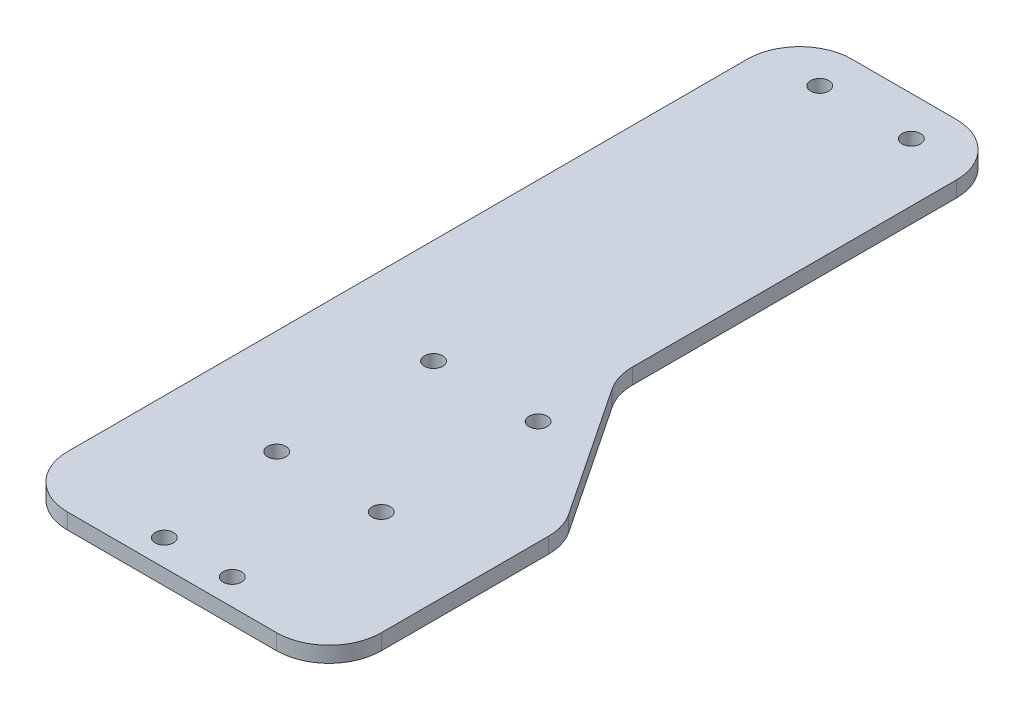
SolidWorks part; units mm, degrees
ref_plane "前视基准面" through (0, 0, 0) normal (0, 0, 1) x (1, 0, 0)
ref_plane "上视基准面" through (0, 0, 0) normal (0, 1, 0) x (1, 0, 0)
ref_plane "右视基准面" through (0, 0, 0) normal (1, 0, 0) x (0, 0, -1)
other "Configuration Table"
sketch "草图1" plane through (0, 0, 0) normal (0, 1, 0) x (1, 0, 0)
  line L0 (32.5794, -69.0423) -> (32.5794, -37.0701)
  line L1 (-17.4206, -79.0423) -> (22.5794, -79.0423)
  line L2 (-27.4206, -69.0423) -> (-27.4206, 60.9577)
  line L3 (-17.4206, 70.9577) -> (2.5794, 70.9577)
  line L4 (12.5794, -1.0146) -> (12.5794, 60.9577)
  line L7 (30.8999, -31.5231) -> (14.2589, -6.5616)
  arc A0 (14.2589, -6.5616) -> (12.5794, -1.0146) centre (22.5794, -1.0146) cw
  arc A1 (32.5794, -37.0701) -> (30.8999, -31.5231) centre (22.5794, -37.0701) ccw
  arc A2 (32.5794, -69.0423) -> (22.5794, -79.0423) centre (22.5794, -69.0423) cw
  arc A3 (-27.4206, 60.9577) -> (-17.4206, 70.9577) centre (-17.4206, 60.9577) cw
  arc A4 (-17.4206, -79.0423) -> (-27.4206, -69.0423) centre (-17.4206, -69.0423) cw
  arc A5 (2.5794, 70.9577) -> (12.5794, 60.9577) centre (2.5794, 60.9577) cw
  point P0 (0, 0)
  point P4 (0, 0)
  point P13 (12.5794, -4.0423)
  point P16 (32.5794, -34.0423)
  point P19 (32.5794, -79.0423)
  point P22 (-27.4206, 70.9577)
  point P25 (-27.4206, -79.0423)
  point P28 (12.5794, 70.9577)
  dimension "D7" = 10
  dimension "D1" = 40
  dimension "D2" = 150
  dimension "D3" = 60
  dimension "D4" = 30
  dimension "D5" = 45
extrude "凸台-拉伸1" add sketch "草图1" along normal blind 3
sketch "草图3" plane through (0, 0, 0) normal (0, -1, 0) x (1, 0, 0)
  circle A0 centre (-7.4206, 49.0423) radius 1.75
  circle A1 centre (-7.4206, 19.0423) radius 1.75
  circle A2 centre (12.5794, 19.0423) radius 1.75
  circle A3 centre (12.5794, 49.0423) radius 1.75
  circle A4 centre (-3.9206, 74.0423) radius 1.75
  circle A5 centre (9.0794, 74.0423) radius 1.75
  circle A6 centre (-16.068, -63.4577) radius 1.75
  circle A7 centre (1.4467, -63.4577) radius 1.75
  dimension "D1" = 20
  dimension "D2" = 20
extrude "切除-拉伸1" cut sketch "草图3" against normal blind 10
